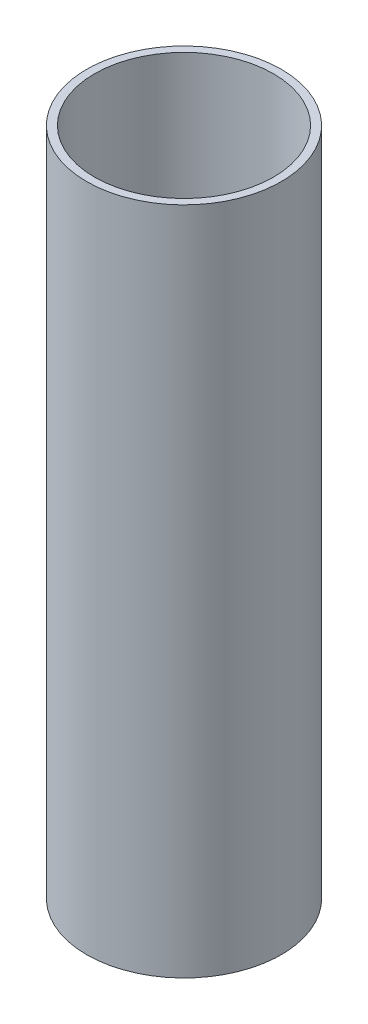
SolidWorks part; units mm, degrees
material "ПВХ 0.007 Смягченный"
ref_plane "Спереди" through (0, 0, 0) normal (0, 0, 1) x (1, 0, 0)
ref_plane "Сверху" through (0, 0, 0) normal (0, 1, 0) x (1, 0, 0)
ref_plane "Справа" through (0, 0, 0) normal (1, 0, 0) x (0, 0, -1)
sketch "Эскиз1" plane through (0, 0, 0) normal (0, 1, 0) x (1, 0, 0)
  circle A0 centre (0, 0) radius 25
  circle A1 centre (0, 0) radius 23
  dimension "ExDBody" = 50
  dimension "InDBody" = 46
extrude "Бобышка-Вытянуть1" add sketch "Эскиз1" along normal blind 172
